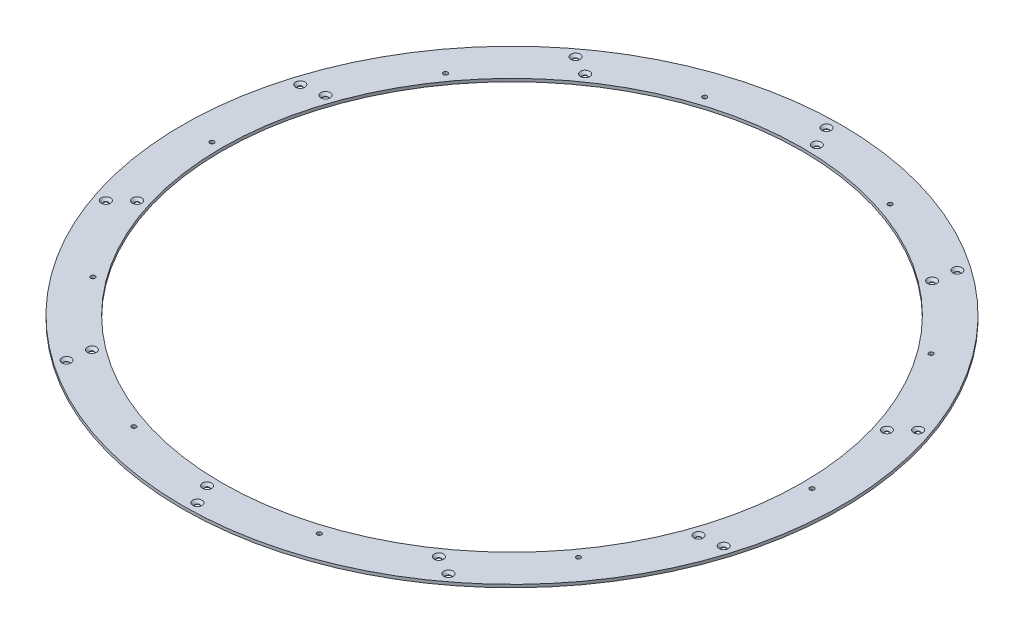
SolidWorks part; units mm, degrees
ref_plane "Front Plane" through (0, 0, 0) normal (0, 0, 1) x (1, 0, 0)
ref_plane "Top Plane" through (0, 0, 0) normal (0, 1, 0) x (1, 0, 0)
ref_plane "Right Plane" through (0, 0, 0) normal (1, 0, 0) x (0, 0, -1)
sketch "Sketch1" plane through (0, 0, 0) normal (0, 1, 0) x (1, 0, 0)
  circle A0 centre (0, 0) radius 295
  circle A1 centre (0, 0) radius 335
  dimension "D1" = 590
  dimension "D2" = 670
extrude "Boss-Extrude1" add sketch "Sketch1" along normal blind 3
hole_wizard "CBORE for M4 SHCS1" positions "Sketch2" profile "Sketch3" counterbore size "M4" standard "ANSI Metric" end condition through all
sketch "Sketch2" plane through (-241.9199, 27, -82.7315) normal (0, 1, 0) x (-0.731, 0, -0.6824)
  point P3 (-104.2581, -380.9603)
  point P9 (33.5365, -252.3327)
  point P15 (69.4093, -67.2773)
  point P21 (-10.3419, 103.5213)
  point P27 (-175.2549, 194.8236)
  point P33 (-362.3384, 171.7553)
  point P39 (-500.133, 43.1278)
  point P45 (-536.0057, -141.9277)
  point P51 (-456.2545, -312.7262)
  point P57 (-291.3416, -404.0286)
sketch "Sketch3" plane through (94.2502, 27, -290.0722) normal (1, 0, 0) x (0, 0, 1)
  line L0 (0, 0) -> (0, 27)
  line L1 (0, 27) -> (2.25, 27)
  line L2 (2.25, 27) -> (2.25, 4)
  line L3 (2.25, 4) -> (4, 4)
  line L4 (4, 4) -> (4, 0)
  line L5 (4, 0) -> (0, 0)
  line L6 (0, -6.35) -> (0, 107.95) construction
  dimension "Thru Hole Dia." = 4.5
  dimension "Thru Hole Depth" = 27
  dimension "C'Bore Dia." = 8
  dimension "C'Bore Depth" = 4
hole_wizard "CSK for M4 Flat Head Machine Screw1" positions "Sketch4" profile "Sketch5" countersink size "M4" standard "ANSI Metric" end condition through all
sketch "Sketch4" plane through (68.2923, 3, -24.8286) normal (0, 1, 0) x (1, 0, 0)
  point P0 (-375.7267, -130.2282)
  point P3 (-378.9643, 70.6068)
  point P6 (-263.5358, 234.9887)
  point P9 (-73.5308, 300.1292)
  point P12 (118.475, 241.1469)
  point P15 (239.1421, 80.5711)
  point P18 (242.3797, -120.2639)
  point P21 (126.9511, -284.6458)
  point P24 (-63.0538, -349.7863)
  point P27 (-255.0596, -290.804)
  point P31 (-359.846, -114.3909)
  point P34 (-356.8077, 74.0849)
  point P37 (-243.5663, 224.7792)
  point P40 (-63.3762, 280.1318)
  point P43 (114.9362, 218.9999)
  point P46 (223.2614, 64.7338)
  point P49 (220.2231, -123.742)
  point P52 (106.9816, -274.4363)
  point P55 (-73.2085, -329.7889)
  point P58 (-251.5208, -268.657)
sketch "Sketch5" plane through (-307.4344, 3, 105.3996) normal (1, 0, 0) x (0, 0, 1)
  line L0 (0, 0) -> (0, 3)
  line L1 (0, 3) -> (2.25, 3)
  line L2 (2.25, 3) -> (2.25, 2.45)
  line L3 (2.25, 2.45) -> (4.7, 0)
  line L4 (4.7, 0) -> (0, 0)
  line L5 (-2.25, 2.45) -> (-4.7, 0) construction
  line L6 (0, -6.35) -> (0, 107.95) construction
  dimension "Thru Hole Dia." = 4.5
  dimension "Thru Hole Depth" = 3
  dimension "Near C'Sink Dia." = 9.4
  dimension "Near C'Sink Angle" = 90
